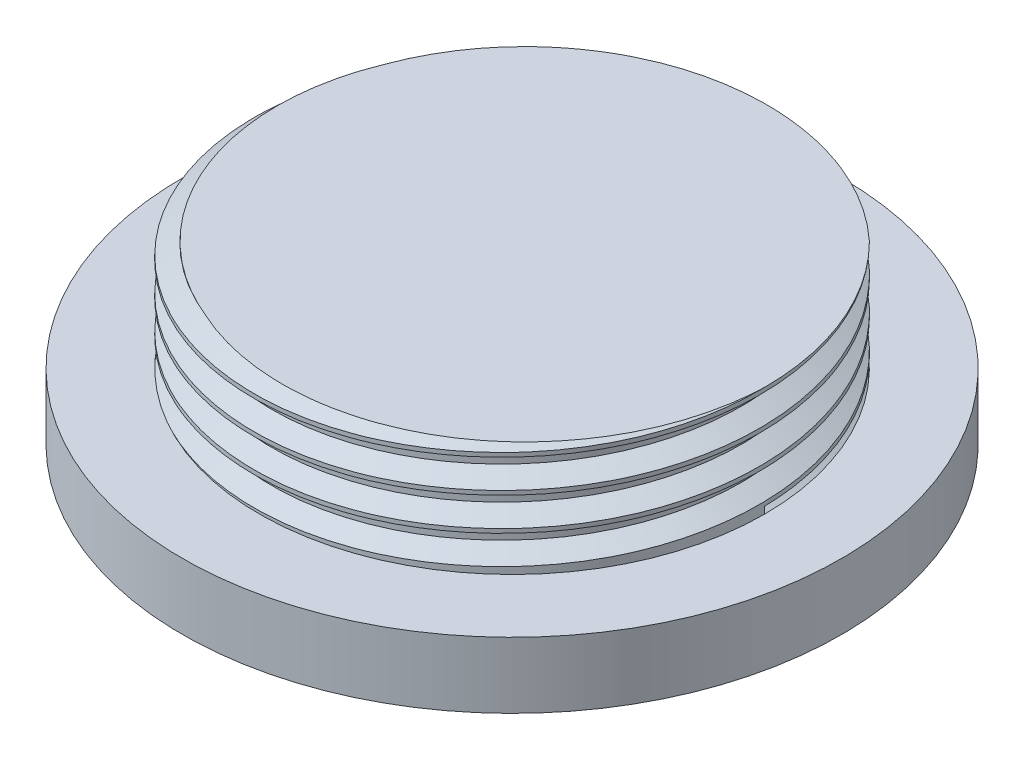
SolidWorks part; units mm, degrees
ref_plane "Alzado" through (0, 0, 0) normal (0, 0, 1) x (1, 0, 0)
ref_plane "Planta" through (0, 0, 0) normal (0, 1, 0) x (1, 0, 0)
ref_plane "Vista lateral" through (0, 0, 0) normal (1, 0, 0) x (0, 0, -1)
sketch "Croquis1" plane through (0, 0, 0) normal (0, 0, 1) x (1, 0, 0)
  line L0 (0, 0) -> (-11.5, 0)
  line L1 (-11.5, 0) -> (-11.5, -5)
  line L2 (-11.5, -5) -> (-15, -5)
  line L3 (-15, -5) -> (-15, -8)
  line L4 (-15, -8) -> (0, -8)
  line L5 (0, -8) -> (0, 0)
  dimension "D1" = 11.5
  dimension "D2" = 5
  dimension "D3" = 15
  dimension "D4" = 3
revolve "Revolución1" add sketch "Croquis1" angle 360 about L5
thread "Rosca1" pitch 1.5 start angle 0, offset 0, length 0, pitch 1.5, diameter 23
ref_plane "Plano1" through (11.5, 0, 0) normal (0, 0, 1) x (1, 0, 0)
sketch "Perfil de rosca1" plane through (11.5, 0, 0) normal (0, 0, 1) x (1, 0, 0)
  line L0 (0, 0) -> (0, 1.5) construction
  line L11 (0, 0) -> (0, 1.3125)
  line L12 (0, 1.3125) -> (-0.8119, 0.8437)
  line L13 (-0.8119, 0.8437) -> (-0.8119, 0.4687)
  line L15 (-0.8119, 0.4687) -> (0, 0)
  line L17 (-0.8119, 0.6562) -> (0, 0.6562) construction
  point P2 (0, 0)
  dimension "Pitch" = 1.5
  dimension "Profile_Angle" = 60
  dimension "Profile_Land" = 0.375
  dimension "Profile_Height" = 0.8119
sketch "Croquis4" plane through (0, -8, 0) normal (0, -1, 0) x (1, 0, 0)
  line L0 (-141.5039, -246.875) -> (-141.5039, -34.875) construction
  line L1 (-138.3656, -237.2134) -> (-138.3656, -25.2134) construction
  line L2 (3.5019, -1.9637) -> (2.8067, -1.7469)
  line L3 (6.7492, -1.63) -> (6.7492, 0.4013) construction
  circle A0 centre (0, 0) radius 7.5 construction
  spline S0 degree 3 poles (5.4783, -3.0026) (5.2939, -3.0997) (4.9059, -2.8843) (4.5014, -2.7858) (4.1969, -2.6771) (3.9677, -2.5968) (3.7603, -2.583) (3.586, -2.5795) (3.4419, -2.7495) (2.7807, -3.1745) (0.8489, -3.9586) (-1.7314, -3.2995) (-3.143, -1.6045) (-4.1204, 0.1202) (-4.8068, 1.6146) (-5.2997, 2.5812) knots 0 0 0 0 0.045509 0.074889 0.092461 0.113664 0.125695 0.137175 0.148043 0.170271 0.305001 0.581101 0.650984 0.7701 1 1 1 1
  spline S1 degree 3 poles (-5.2997, 2.5812) (-4.6157, 2.7162) (-3.265, 2.754) (-0.5305, 2.721) (2.2876, 1.5473) (3.6836, -0.6599) (4.0278, -1.7191) (3.8973, -2.2471) (4.1019, -2.3029) (4.2825, -2.3865) (4.5592, -2.4756) (4.9567, -2.6175) (5.5058, -2.7047) (5.4783, -3.0026) knots 0 0 0 0 0.154785 0.300688 0.611266 0.783841 0.856255 0.872093 0.881128 0.897547 0.918952 0.943746 1 1 1 1
  spline S2 degree 3 poles (3.1974, -2.4352) (2.9687, -2.7045) (2.312, -3.0014) (1.6373, -3.2496) (1.2596, -3.2365) knots 0 0 0 0 0.481114 1 1 1 1
  spline S3 degree 1 poles (3.1974, -2.4352) (2.7927, -2.2546) knots 0 0 1 1
  spline S4 degree 3 poles (2.7927, -2.2546) (2.6241, -2.3497) (2.3856, -2.5367) (1.85, -2.8253) (1.4697, -3.0048) (1.2596, -3.2365) knots 0 0 0 0 0.317739 0.494985 1 1 1 1
  spline S5 degree 3 poles (3.5019, -1.9637) (3.5448, -1.674) (3.479, -1.2338) (3.1676, -0.5653) (2.9266, -0.1902) (2.7588, 0.0631) knots 0 0 0 0 0.395874 0.586576 1 1 1 1
  spline S6 degree 3 poles (2.7588, 0.0631) (2.7118, -0.261) (2.7882, -0.8634) (2.7647, -1.4686) (2.8067, -1.7469) knots 0 0 0 0 0.536589 1 1 1 1
  spline S7 degree 3 poles (2.3326, -2.0574) (2.2044, -2.2378) (1.909, -2.4192) (1.5011, -2.7059) (1.0756, -2.9003) (0.8303, -3.1358) (0.6574, -3.2005) knots 0 0 0 0 0.316444 0.507916 0.734242 1 1 1 1
  spline S8 degree 3 poles (0.6574, -3.2005) (0.275, -3.2819) (-0.1224, -3.2165) (-0.488, -3.0946) knots 0 0 0 0 1 1 1 1
  spline S9 degree 3 poles (-0.488, -3.0946) (-0.3118, -2.9094) (0.0121, -2.6557) (0.488, -2.3296) (0.9313, -2.0449) (1.2168, -1.8054) (1.3936, -1.7022) knots 0 0 0 0 0.326234 0.525 0.738479 1 1 1 1
  spline S10 degree 3 poles (2.3326, -2.0574) (2.1712, -2.0169) (1.8613, -1.8893) (1.5526, -1.7596) (1.3936, -1.7022) knots 0 0 0 0 0.495129 1 1 1 1
  spline S11 degree 3 poles (2.4463, -1.4679) (2.1602, -1.3858) (1.8851, -1.2699) (1.6149, -1.1462) knots 0 0 0 0 1 1 1 1
  spline S12 degree 3 poles (1.6149, -1.1462) (1.6211, -0.8204) (1.4845, -0.3144) (1.4411, 0.4808) (1.3806, 0.9503) (1.3936, 1.227) knots 0 0 0 0 0.405946 0.652936 1 1 1 1
  spline S13 degree 3 poles (2.4463, -1.4679) (2.4297, -1.1969) (2.4007, -0.583) (2.3637, 0.0306) (2.3326, 0.3724) knots 0 0 0 0 0.441733 1 1 1 1
  spline S14 degree 3 poles (2.3326, 0.3724) (2.294, 0.5532) (2.0913, 0.7421) (1.7933, 1.0664) (1.531, 1.1474) (1.3936, 1.227) knots 0 0 0 0 0.397173 0.631475 1 1 1 1
  spline S15 degree 3 poles (0.8942, -1.4679) (0.6937, -1.6252) (0.3522, -1.8797) (-0.0722, -2.2464) (-0.5217, -2.4886) (-0.7478, -2.7452) (-0.9161, -2.858) knots 0 0 0 0 0.334549 0.559859 0.734194 1 1 1 1
  spline S16 degree 3 poles (-0.9161, -2.858) (-1.1399, -2.8474) (-1.4251, -2.6065) (-1.7638, -2.4555) (-1.8736, -2.3379) knots 0 0 0 0 0.568618 1 1 1 1
  spline S17 degree 3 poles (0.8942, -1.4679) (0.7162, -1.3644) (0.3037, -1.2371) (-0.0231, -0.9544) (-0.2084, -0.8427) knots 0 0 0 0 0.486655 1 1 1 1
  spline S18 degree 3 poles (-1.8736, -2.3379) (-1.7031, -2.1696) (-1.2004, -1.6133) (-0.5531, -1.2169) (-0.2084, -0.8427) knots 0 0 0 0 0.321358 1 1 1 1
  spline S19 degree 3 poles (-0.7366, -0.6125) (-0.8374, -0.8429) (-1.1429, -1.093) (-1.7041, -1.5013) (-1.9371, -1.9063) (-2.2093, -2.0574) knots 0 0 0 0 0.350602 0.564021 1 1 1 1
  spline S20 degree 3 poles (-2.2093, -2.0574) (-2.4128, -1.9247) (-2.6083, -1.5393) (-2.9064, -1.2329) (-3.007, -1.0685) knots 0 0 0 0 0.548239 1 1 1 1
  spline S21 degree 3 poles (-3.007, -1.0685) (-2.7766, -0.9212) (-2.453, -0.7138) (-1.9974, -0.3665) (-1.7257, -0.2309) (-1.5957, -0.0909) knots 0 0 0 0 0.477748 0.66972 1 1 1 1
  spline S22 degree 3 poles (-0.7366, -0.6125) (-0.9987, -0.3959) (-1.3491, -0.3293) (-1.5957, -0.0909) knots 0 0 0 0 1 1 1 1
  spline S23 degree 3 poles (-3.1948, -0.7518) (-2.9653, -0.5263) (-2.5219, -0.351) (-2.0837, -0.0432) (-2.0218, 0.1404) knots 0 0 0 0 0.616737 1 1 1 1
  spline S24 degree 3 poles (-3.1948, -0.7518) (-3.3879, -0.5328) (-3.5151, -0.0639) (-3.792, 0.3277) (-3.8787, 0.4982) knots 0 0 0 0 0.597562 1 1 1 1
  spline S25 degree 3 poles (-3.8787, 0.4982) (-3.5903, 0.523) (-3.45, 0.9435) (-3.145, 0.8692) knots 0 0 0 0 1 1 1 1
  spline S26 degree 3 poles (-2.0218, 0.1404) (-2.3504, 0.4588) (-2.8239, 0.5402) (-3.145, 0.8692) knots 0 0 0 0 1 1 1 1
  spline S27 degree 3 poles (-3.5481, 1.1472) (-3.6438, 1.1098) (-3.9259, 0.7264) (-4.1677, 1.0126) (-4.332, 1.3708) (-4.5106, 1.6961) (-4.6305, 1.9248) knots 0 0 0 0 0.310868 0.394958 0.558357 1 1 1 1
  spline S28 degree 3 poles (-3.5481, 1.1472) (-3.6972, 1.2876) (-4.0477, 1.5622) (-4.4009, 1.8394) (-4.6305, 1.9248) knots 0 0 0 0 0.458358 1 1 1 1
  spline S29 degree 3 poles (-3.4575, 1.6984) (-3.4446, 1.8696) (-3.4675, 2.0387) (-3.448, 2.3872) (-3.6524, 2.3818) (-3.8288, 2.4231) (-4.1502, 2.3868) (-4.3925, 2.4738) (-4.5626, 2.4185) knots 0 0 0 0 0.268265 0.385213 0.459279 0.566834 0.712658 1 1 1 1
  spline S30 degree 3 poles (-3.4575, 1.6984) (-3.6626, 1.8217) (-4.0434, 2.0449) (-4.3804, 2.3307) (-4.5626, 2.4185) knots 0 0 0 0 0.544609 1 1 1 1
  spline S31 degree 3 poles (-1.9071, 0.7093) (-2.1368, 0.7834) (-2.3761, 1.0401) (-2.8146, 1.1693) (-2.9573, 1.4734) (-3.0183, 1.8581) (-3.0616, 2.1728) (-3.0616, 2.3642) knots 0 0 0 0 0.312979 0.470055 0.574114 0.74199 1 1 1 1
  spline S32 degree 3 poles (-1.9071, 0.7093) (-2.0023, 0.9795) (-1.9569, 1.3762) (-2.1088, 1.8597) (-2.2019, 2.1042) (-2.2441, 2.3369) (-2.5907, 2.4073) (-2.826, 2.3281) (-3.0616, 2.3642) knots 0 0 0 0 0.341457 0.475561 0.607155 0.678259 0.727851 1 1 1 1
  spline S33 degree 3 poles (-0.6749, 0) (-0.8573, 0.0994) (-1.0994, 0.2038) (-1.389, 0.4007) (-1.5243, 0.6723) (-1.613, 1.0358) (-1.5993, 1.6148) (-1.8272, 1.9939) (-1.828, 2.2736) knots 0 0 0 0 0.225465 0.291568 0.375328 0.547817 0.698545 1 1 1 1
  spline S34 degree 3 poles (-0.6749, 0) (-0.6758, 0.2749) (-0.8461, 0.6671) (-0.8655, 1.2155) (-0.9551, 1.6206) (-0.9955, 1.9176) (-1.0252, 2.2142) (-1.4123, 2.234) (-1.6149, 2.3137) (-1.828, 2.2736) knots 0 0 0 0 0.271622 0.416103 0.548394 0.680553 0.734696 0.811447 1 1 1 1
  spline S35 degree 3 poles (1.113, -0.8427) (0.903, -0.7713) (0.5455, -0.6815) (0.1628, -0.4104) (-0.161, -0.3215) (-0.3407, 0.033) (-0.3278, 0.4758) (-0.5112, 1.1635) (-0.4708, 1.6819) (-0.5708, 2.0086) knots 0 0 0 0 0.180625 0.286973 0.37907 0.43135 0.590976 0.729094 1 1 1 1
  spline S36 degree 3 poles (1.113, -0.8427) (1.1252, -0.5594) (1.0712, -0.1167) (1.0193, 0.5379) (0.905, 1.0219) (0.9924, 1.5087) (0.6827, 1.6954) (0.3964, 1.8042) (-0.0493, 1.8965) (-0.3527, 2.0617) (-0.5708, 2.0086) knots 0 0 0 0 0.213489 0.340134 0.492639 0.605071 0.657073 0.746886 0.84184 1 1 1 1
  text T0 "LL" font "Unispace" height in points 9
  point P205 (5.8151, -1.7469)
  point P208 (6.3274, -1.7469)
  point P210 (6.7492, -1.63)
  dimension "D1" = 15
extrude "Saliente-Extruir1" add sketch "Croquis4" along normal blind 2
